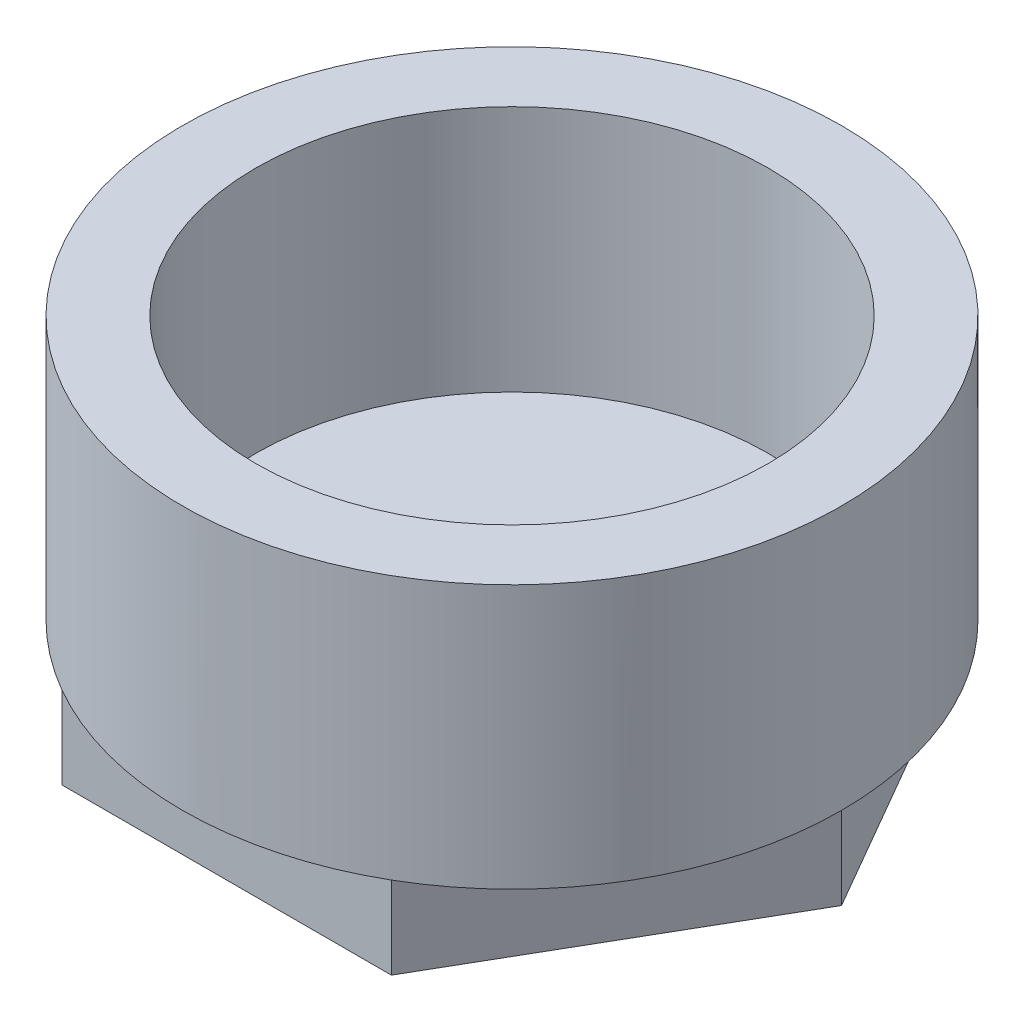
SolidWorks part; units mm, degrees
material "1.0035 (S185)"
ref_plane "Piano frontale" through (0, 0, 0) normal (0, 0, 1) x (1, 0, 0)
ref_plane "Piano superiore" through (0, 0, 0) normal (0, 1, 0) x (1, 0, 0)
ref_plane "Piano destro" through (0, 0, 0) normal (1, 0, 0) x (0, 0, -1)
sketch "Schizzo1" plane through (0, 0, 0) normal (0, 0, 1) x (1, 0, 0)
  line L0 (0, 0) -> (-20, 0)
  line L1 (-20, 0) -> (-20, 21)
  line L2 (-20, 21) -> (-15.5465, 21)
  line L3 (-15.5465, 21) -> (-15.5465, 6)
  line L4 (-15.5465, 6) -> (0, 6)
  line L5 (0, 6) -> (0, 0)
  line L6 (0, 0) -> (0, 10.8439) construction
  dimension "D1" = 40
  dimension "D2" = 31.093
  dimension "D3" = 15
  dimension "D4" = 21
revolve "Rivoluzione1" add sketch "Schizzo1" angle 360 about L6
sketch "Schizzo2" plane through (0, 0, 0) normal (0, -1, 0) x (1, 0, 0)
  circle A0 centre (0, 0) radius 3.175
  dimension "D1" = 6.35
extrude "Taglio-Estrusione1" cut sketch "Schizzo2" against normal blind 10
sketch "Schizzo3" plane through (0, 0, 0) normal (0, -1, 0) x (1, 0, 0)
  circle A0 centre (0, 0) radius 1.019
  circle A1 centre (0, 0) radius 1.5875
  dimension "D1" = 3.175
extrude "Estrusione-Estrusione1" [suppressed] add sketch "Schizzo3" along normal blind 8
sketch "Schizzo4" plane through (0, 0, 0) normal (0, 0, 1) x (1, 0, 0)
  line L0 (0, 0) -> (0, -9.8437)
sketch "Schizzo5" plane through (0, 0, 0) normal (0, -1, 0) x (-1, 0, 0)
  line L0 (10, 17.3205) -> (20, 0)
  line L1 (20, 0) -> (10, -17.3205)
  line L2 (10, -17.3205) -> (-10, -17.3205)
  line L3 (-10, -17.3205) -> (-20, 0)
  line L4 (-20, 0) -> (-10, 17.3205)
  line L5 (-10, 17.3205) -> (10, 17.3205)
  circle A0 centre (0, 0) radius 20 construction
  circle A1 centre (0, 0) radius 15
  circle M9 centre (0, 0) radius 20
extrude "Taglio-Estrusione2" cut sketch "Schizzo5" against normal blind 5 contours L5 M9 | L0 M9 | L1 M9 | L2 M9 | L3 M9 | L4 M9 region at (-15.9337, 0, -9.1994) region at (0, 0, -18.3987) region at (-15.9337, 0, 9.1994) region at (15.9337, 0, -9.1994) region at (0, 0, 18.3987) region at (15.9337, 0, 9.1994)
